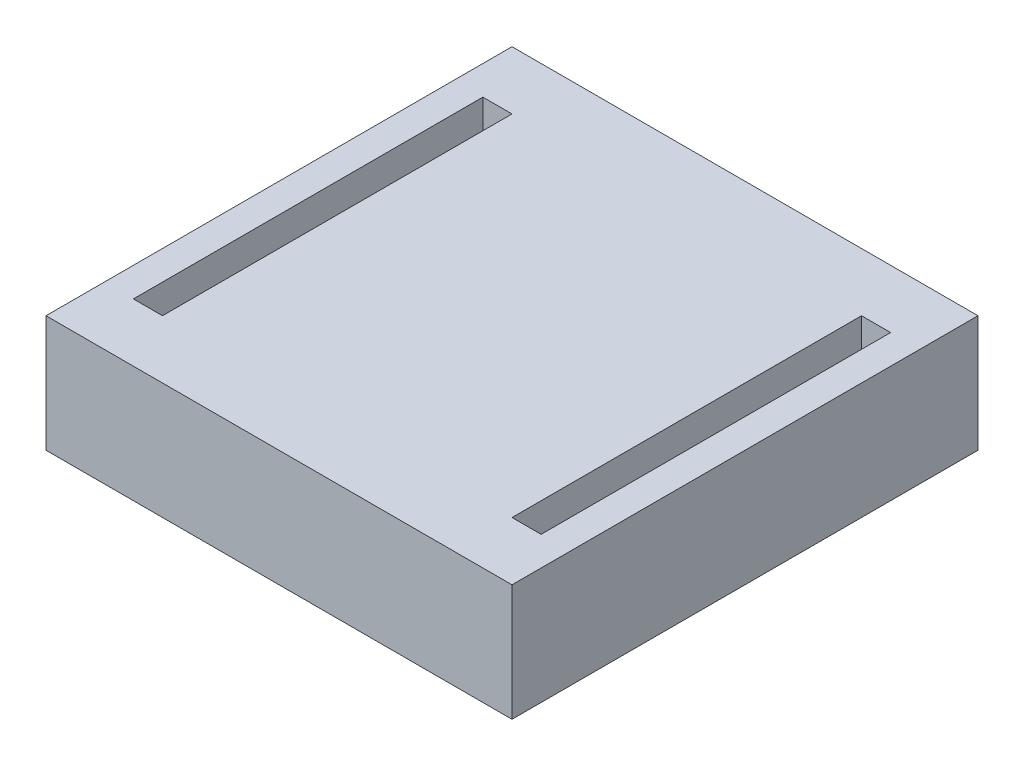
SolidWorks part; units mm, degrees
ref_plane "Front Plane" through (0, 0, 0) normal (0, 0, 1) x (1, 0, 0)
ref_plane "Top Plane" through (0, 0, 0) normal (0, 1, 0) x (1, 0, 0)
ref_plane "Right Plane" through (0, 0, 0) normal (1, 0, 0) x (0, 0, -1)
sketch "Sketch1" plane through (0, 0, 0) normal (0, 1, 0) x (1, 0, 0)
  line L0 (-0.8242, 0) -> (19.1758, 0)
  line L1 (-0.8242, 0) -> (-0.8242, 20)
  line L2 (-0.8242, 20) -> (19.1758, 20)
  line L3 (19.1758, 20) -> (19.1758, 0)
  line L4 (-0.8242, 20) -> (1.675, 20)
  line L5 (1.675, 17.5) -> (1.675, 2.5)
  line L6 (19.1758, 20) -> (16.6758, 20)
  line L7 (16.6758, 17.5) -> (16.6758, 2.5)
  line L8 (-0.8242, 20) -> (0.4254, 20)
  line L9 (0.425, 17.5) -> (0.425, 2.5)
  line L10 (17.9258, 17.5) -> (17.9258, 2.5)
  line L12 (16.6758, 17.5) -> (17.9258, 17.5)
  line L14 (16.6758, 2.5) -> (17.9258, 2.5)
  line L16 (1.675, 17.5) -> (0.425, 17.5)
  line L18 (1.675, 2.5) -> (0.425, 2.5)
  line L19 (12.1758, 14.75) -> (15.1758, 14.75)
  line L20 (6.1758, 14.75) -> (3.1758, 14.75)
  line L21 (3.1758, 14.75) -> (3.1758, 20)
  line L24 (6.1758, 14.75) -> (12.1758, 14.75)
  line L26 (15.1758, 14.75) -> (15.1758, 20)
  line L27 (3.1758, 5.25) -> (3.1758, 0)
  line L28 (14.1758, 20) -> (9.1758, 20)
  line L29 (15.1758, 5.25) -> (15.1758, 0)
  line L31 (12.1758, 5.25) -> (6.1758, 5.25)
  line L32 (6.1758, 5.25) -> (3.1758, 5.25)
  line L33 (12.1758, 5.25) -> (15.1758, 5.25)
  line L34 (15.1758, 5.25) -> (15.1758, 0)
  circle A0 centre (6.1758, 17.5) radius 0.75
  circle A1 centre (12.1758, 17.5) radius 0.75
  circle A2 centre (6.1758, 2.5) radius 0.75
  circle A3 centre (12.1758, 2.5) radius 0.75
  point P22 (0, 0)
  point P35 (0, 0)
  dimension "D1" = 20
  dimension "D2" = 20
  dimension "D3" = 15
  dimension "D4" = 15
  dimension "D5" = 15.0008
  dimension "D6" = 15.0008
  dimension "D7" = 1.25
  dimension "D8" = 1.25
  dimension "D10" = 3
  dimension "D11" = 4.5
sketch "Sketch2" plane through (0, 0, 0) normal (0, 1, 0) x (1, 0, 0)
  line L0 (1.675, 17.5) -> (4.675, 17.5)
  line L1 (4.675, 17.5) -> (7.4624, 17.5)
  line L2 (7.4624, 17.5) -> (10.4624, 17.5)
  line L3 (13.4624, 17.5) -> (10.4624, 17.5)
  line L4 (13.4624, 17.5) -> (16.2609, 17.5)
  point P8 (0, 0)
extrude "Boss-Extrude5" add sketch "Sketch1" along normal blind 5 contours L33 L31 L32 L27 L0 L29 A3 A2 | L19 L26 L2 L21 L20 L24 A1 A0 | L31 L33 L29 L0 L3 L2 L26 L19 L24 L20 L21 L4 L1 L27 L32 L14 L7 L12 L10 L5 L18 L9 L16 | A2 | A0 | A3 | A1 region at (9.1759, 0, -10) region at (9.1758, 0, -2.6324) region at (9.1758, 0, -17.3676)
